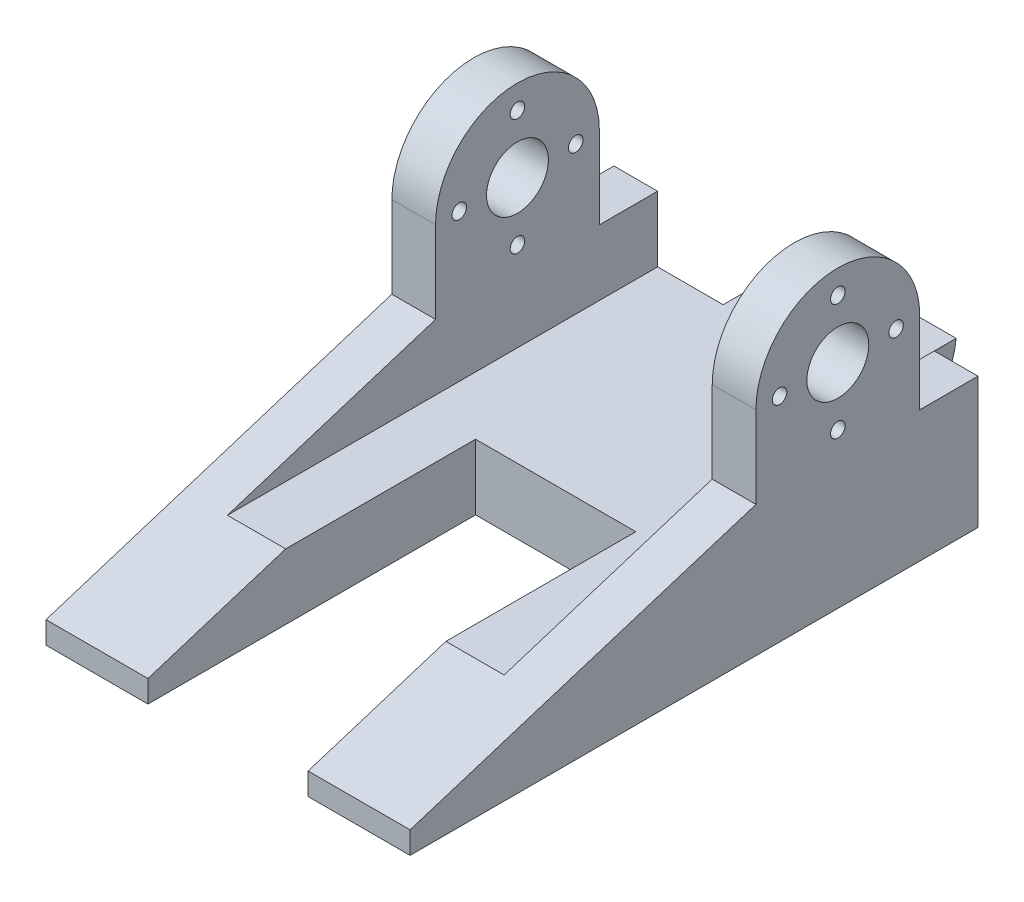
SolidWorks part; units mm, degrees
ref_plane "Front Plane" through (0, 0, 0) normal (0, 0, 1) x (1, 0, 0)
ref_plane "Top Plane" through (0, 0, 0) normal (0, 1, 0) x (1, 0, 0)
ref_plane "Right Plane" through (0, 0, 0) normal (1, 0, 0) x (0, 0, -1)
sketch "Sketch1" plane through (0, 0, 0) normal (0, 0, 1) x (1, 0, 0)
  line L1 (-25, 0) -> (25, 0)
  line L2 (-25, 0) -> (-25, -170)
  line L3 (-25, -170) -> (25, -170)
  line L4 (25, 0) -> (25, -170)
  dimension "D1" = 170
  dimension "D2" = 50
extrude "Boss-Extrude1" add sketch "Sketch1" against normal blind 55
sketch "Sketch2" plane through (0, 0, 0) normal (0, 0, 1) x (1, 0, 0)
  line L0 (25, 0) -> (-25, 0) construction
  line L1 (-17, 0) -> (17, 0)
  line L2 (-17, 0) -> (-17, -27)
  line L3 (-17, -27) -> (17, -27)
  line L4 (17, 0) -> (17, -27)
  line L5 (-25, 0) -> (-25, -170) construction
  dimension "D1" = 8
  dimension "D2" = 34
  dimension "D3" = 27
extrude "Cut-Extrude1" cut sketch "Sketch2" against normal through all
sketch "Sketch3" plane through (25, 0, 0) normal (1, 0, 0) x (0, 0, -1)
  line L0 (0, -170) -> (0, 0) construction
  line L1 (55, -27) -> (0, -27)
  line L2 (55, -27) -> (55, -24)
  line L3 (55, -24) -> (0, -24)
  line L4 (0, -27) -> (0, -24)
  line L5 (55, -170) -> (55, 0) construction
  line L7 (0, 0) -> (10, 0)
  line L8 (0, 0) -> (0, -24)
  line L9 (0, -24) -> (10, -24)
  line L10 (10, 0) -> (10, -24)
  line L11 (55, 0) -> (45, 0)
  line L12 (55, 0) -> (55, -24)
  line L13 (55, -24) -> (45, -24)
  line L14 (45, 0) -> (45, -24)
  circle A0 centre (27.5, -12.75) radius 10.25
  circle A1 centre (27.5, -12.75) radius 4.25
  circle A2 centre (27.5, -12.75) radius 8
  circle A3 centre (27.5, -4.75) radius 1
  circle A4 centre (35.5, -12.75) radius 1
  circle A5 centre (27.5, -20.75) radius 1
  circle A6 centre (19.5, -12.75) radius 1
  point P32 (27.5, -12.75)
  line M7 (0, 0) -> (0, -170)
  line M9 (55, -170) -> (55, 0)
  line M10 (55, 0) -> (0, 0)
  dimension "D2" = 11.25
  dimension "D3" = 27.5
  dimension "D4" = 20.5
  dimension "D7" = 8.5
  dimension "D8" = 16
  dimension "D9" = 4
  dimension "D1" = 3
  dimension "D5" = 10
  dimension "D6" = 10
extrude "Cut-Extrude2" cut sketch "Sketch3" against normal through all contours L14 L3 M10 M9 | L10 L3 M10 M7 | A2 A6 | A2 A6 | A1 | A2 A5 | A2 A5 | A2 A4 | A2 A4 | A2 A3 | A2 A3 region at (25, -12, -50) region at (25, -12, -5) region at (25, -12.75, -27.5) region at (25, -12.75, -35.0645) region at (25, -12.75, -35.913) region at (25, -5.1855, -27.5) region at (25, -4.337, -27.5) region at (25, -21.163, -27.5) region at (25, -20.3145, -27.5) region at (25, -12.75, -19.9355) region at (25, -12.75, -19.087)
sketch "Sketch4" plane through (0, 0, -10) normal (0, 0, 1) x (1, 0, 0)
  line L0 (-25, -24) -> (-17, -24) construction
  line L1 (-17, 0) -> (-19, 0)
  line L2 (-17, 0) -> (-17, -24)
  line L3 (-17, -24) -> (-19, -24)
  line L4 (-19, 0) -> (-19, -24)
  line L5 (0, 0) -> (0, -13.53) construction
  line L6 (19, 0) -> (19, -24)
  line L7 (17, -24) -> (19, -24)
  line L8 (17, 0) -> (17, -24)
  line L9 (17, 0) -> (19, 0)
  dimension "D1" = 2
extrude "Cut-Extrude3" cut sketch "Sketch4" against normal through all
sketch "Sketch5" plane through (25, 0, 0) normal (1, 0, 0) x (0, 0, -1)
  line L1 (10, 0) -> (45, 0)
  line L2 (10, 0) -> (10, -24)
  line L3 (10, -24) -> (45, -24)
  line L4 (45, 0) -> (45, -24)
  line L5 (38.75, -12.75) -> (38.75, -24)
  line L6 (16.25, -12.75) -> (10, -12.75)
  line L7 (16.25, -12.75) -> (16.25, -24)
  line L8 (16.25, -24) -> (10, -24)
  line L9 (10, -12.75) -> (10, -24)
  line L10 (38.75, -12.75) -> (45, -12.75)
  line L11 (38.75, -12.75) -> (38.75, -24)
  line L12 (38.75, -24) -> (45, -24)
  line L13 (45, -12.75) -> (45, -24)
  circle A0 centre (27.5, -12.75) radius 11.25
  line M8 (45, -24) -> (45, 0)
  line M9 (45, 0) -> (10, 0)
  line M10 (10, 0) -> (10, -24)
  dimension "D1" = 22.5
extrude "Cut-Extrude4" cut sketch "Sketch5" against normal through all contours A0 L10 L4 L6 M9 M10 | L7 L6 L2 L3 | L10 L5 L3 M8 region at (25, -0.3725, -27.5) region at (25, -18.375, -13.125) region at (25, -18.375, -41.875)
sketch "Sketch6" plane through (0, 0, 0) normal (0, 0, 1) x (1, 0, 0)
  line L1 (-19, -24) -> (19, -24)
  line L2 (-19, -24) -> (-19, -34)
  line L3 (-19, -34) -> (19, -34)
  line L4 (19, -24) -> (19, -34)
  dimension "D1" = 10
extrude "Cut-Extrude5" cut sketch "Sketch6" against normal through all
sketch "Sketch8" plane through (25, 0, 0) normal (1, 0, 0) x (0, 0, -1)
  line L0 (55, -170) -> (55, -24) construction
  line L1 (0, -170) -> (0, -24) construction
  line L2 (41.75, -132.5) -> (13.25, -132.5)
  line L3 (27.5, -132.5) -> (27.5, -179)
  line L4 (41.75, -179) -> (13.25, -179)
  line L5 (13.25, -132.5) -> (13.25, -179)
  line L7 (41.75, -132.5) -> (41.75, -179)
  line L11 (27.5, -167.75) -> (55, -167.75)
  line L12 (27.5, -167.75) -> (27.5, -170)
  line L13 (27.5, -170) -> (55, -170)
  line L14 (55, -167.75) -> (55, -170)
  line L16 (27.5, -167.75) -> (0, -167.75)
  line L17 (27.5, -167.75) -> (27.5, -170)
  line L18 (27.5, -170) -> (0, -170)
  line L19 (0, -167.75) -> (0, -170)
  circle A0 centre (27.5, -167.75) radius 10.25
  circle A1 centre (27.5, -12.75) radius 10.25
  line M4 (0, -24) -> (0, -170)
  line M5 (0, -170) -> (55, -170)
  line M6 (55, -170) -> (55, -24)
  dimension "D1" = 27.5
  dimension "D2" = 20.5
  dimension "D3" = 155
  dimension "D4" = 14.25
  dimension "D5" = 11.25
  dimension "D6" = 46.5
  dimension "D7" = 13.25
extrude "Cut-Extrude7" cut sketch "Sketch8" against normal through all contours A0 L3 L2 L5 L16 | A0 L11 L7 L2 L3 | L11 L7 M5 M6 | L5 L16 M4 M5 | A0 L16 L5 M5 | A0 L13 L7 L11 | L3 A0 L16 | L11 A0 L3 | L16 A0 L18 L3 | A0 L11 L3 M5 region at (25, -147.5157, -35.1704) region at (25, -147.5157, -19.8296) region at (25, -168.875, -48.375) region at (25, -168.8865, -39.7079) region at (25, -163.3998, -31.8502) region at (25, -163.3998, -23.1498) region at (25, -168.8704, -32.5838) region at (25, -168.8865, -15.2921) region at (25, -168.875, -6.625) region at (25, -168.8704, -22.4162)
sketch "Sketch9" plane through (0, 0, 0) normal (0, 0, 1) x (1, 0, 0)
  line L0 (-25, -167.75) -> (25, -167.75) construction
  line L1 (17, -167.75) -> (-17, -167.75)
  line L2 (17, -167.75) -> (17, -132.5)
  line L3 (17, -132.5) -> (-17, -132.5)
  line L4 (-17, -167.75) -> (-17, -132.5)
  line L5 (-25, -132.5) -> (25, -132.5) construction
  line L7 (-25, -24) -> (-25, -167.75) construction
  line L9 (25, -167.75) -> (25, -24) construction
  dimension "D1" = 8
  dimension "D2" = 8
extrude "Cut-Extrude8" cut sketch "Sketch9" against normal through all
sketch "Sketch11" plane through (25, 0, 0) normal (1, 0, 0) x (0, 0, -1)
  line L0 (27.5, -157.5) -> (27.5, -147.5)
  line L2 (27.5, -147.5) -> (55, -147.5)
  line L3 (27.5, -147.5) -> (27.5, -167.75)
  line L4 (27.5, -167.75) -> (55, -167.75)
  line L5 (55, -147.5) -> (55, -167.75)
  line L6 (27.5, -147.5) -> (0, -147.5)
  line L7 (27.5, -147.5) -> (27.5, -167.75)
  line L8 (27.5, -167.75) -> (0, -167.75)
  line L9 (0, -147.5) -> (0, -167.75)
  circle A0 centre (27.5, -167.75) radius 10.25
  arc A1 (38.75, -12.75) -> (16.25, -12.75) centre (27.5, -12.75) ccw construction
  line M1 (0, -167.75) -> (13.25, -167.75)
  line M2 (13.25, -167.75) -> (13.25, -132.5)
  line M4 (41.75, -132.5) -> (41.75, -167.75)
  line M5 (41.75, -167.75) -> (55, -167.75)
  line M6 (55, -167.75) -> (55, -24)
  line M12 (0, -24) -> (0, -167.75)
  dimension "D1" = 155
  dimension "D2" = 20.5
  dimension "D3" = 10
extrude "Cut-Extrude9" cut sketch "Sketch11" against normal through all contours A0 L0 L6 L8 M2 | A0 L4 L2 L0 M4 | L2 M4 M5 M6 | L6 M2 M12 M1 region at (25, -155.3124, -19.2638) region at (25, -155.3124, -35.7362) region at (25, -157.625, -48.375) region at (25, -157.625, -6.625)
sketch "Sketch12" plane through (25, 0, 0) normal (1, 0, 0) x (0, 0, -1)
  line L1 (13.25, -132.5) -> (41.75, -132.5)
  line L2 (13.25, -132.5) -> (13.25, -147.5)
  line L3 (13.25, -147.5) -> (41.75, -147.5)
  line L4 (41.75, -132.5) -> (41.75, -147.5)
extrude "Boss-Extrude2" add sketch "Sketch12" against normal blind 8
ref_plane "Plane1" through (0, 0, 0) normal (1, 0, 0) x (0, 0, -1)
mirror "Mirror1" about plane through (0, 0, 0) normal (1, 0, 0) of "Boss-Extrude2"
sketch "Sketch14" plane through (0, 0, 0) normal (0, 0, 1) x (1, 0, 0)
  line L0 (17, -148.55) -> (17, -158.75) construction
  line L1 (-17, -132.5) -> (17, -132.5)
  line L2 (-17, -132.5) -> (-17, -147.5)
  line L3 (-17, -147.5) -> (17, -147.5)
  line L4 (17, -132.5) -> (17, -147.5)
  line L5 (-17, -147.5) -> (17, -147.5)
  line L6 (-17, -147.5) -> (-17, -157.75)
  line L7 (-17, -157.75) -> (17, -157.75)
  line L8 (17, -147.5) -> (17, -157.75)
  line M11 (-17, -147.5) -> (-17, -132.5)
  line M12 (-17, -132.5) -> (17, -132.5)
  line M13 (17, -132.5) -> (17, -147.5)
  dimension "D1" = 10.25
extrude "Boss-Extrude3" add sketch "Sketch14" against normal blind 13.25 contours L3 M11 M13 M12 | L8 L3 L6 L7 region at (0, -140, 0) region at (0, -152.625, 0)
ref_plane "Plane2" through (0, 0, -27.5) normal (0, 0, 1) x (1, 0, 0)
mirror "Mirror2" about plane through (0, 0, -27.5) normal (0, 0, 1) of "Boss-Extrude3"
sketch "Sketch16" plane through (25, 0, 0) normal (1, 0, 0) x (0, 0, -1)
  line L0 (41.75, -132.5) -> (13.25, -132.5) construction
  line L1 (13.25, -132.5) -> (13.25, -147.5) construction
  circle A1 centre (16.5, -135.75) radius 2.5
  circle A2 centre (16.5, -135.75) radius 4.5
  circle A3 centre (38.5, -135.75) radius 4.5
  dimension "D1" = 3.25
  dimension "D2" = 3.25
  dimension "D3" = 2
extrude "Cut-Extrude13" cut sketch "Sketch16" against normal blind 8 contours A1 | A2 A1 | A3 region at (25, -135.75, -16.5) region at (25, -135.75, -12.1273) region at (25, -135.75, -38.5)
mirror "Mirror3" about plane through (0, 0, 0) normal (1, 0, 0) of "Cut-Extrude13"
sketch "Sketch17" plane through (25, 0, 0) normal (1, 0, 0) x (0, 0, -1)
  line L0 (55, -147.5) -> (55, -24) construction
  line L1 (27.5, -1.5) -> (55, -1.5)
  line L2 (27.5, -1.5) -> (27.5, -51.5)
  line L3 (27.5, -51.5) -> (55, -51.5)
  line L4 (55, -1.5) -> (55, -51.5)
  line L8 (55, -51.5) -> (0, -51.5)
  line L9 (55, -51.5) -> (55, -157.75)
  line L10 (55, -157.75) -> (0, -157.75)
  line L11 (0, -51.5) -> (0, -157.75)
  arc A0 (38.75, -12.75) -> (16.25, -12.75) centre (27.5, -12.75) ccw construction
  circle M2 centre (16.5, -135.75) radius 4.5
  circle M3 centre (38.5, -135.75) radius 4.5
  line M4 (0, -147.5) -> (55, -147.5)
  line M5 (55, -147.5) -> (55, -24)
  line M11 (0, -24) -> (0, -147.5)
  dimension "D1" = 50
extrude "Cut-Extrude15" cut sketch "Sketch17" against normal through all contours L3 L8 M11 M4 M5 M2 M3 | L11 L10 L9 M4 | M3 | M2 region at (25, -98.6049, -27.5) region at (25, -152.625, -27.5) region at (25, -135.75, -16.5) region at (25, -135.75, -38.5)
sketch "Sketch18" plane through (25, 0, 0) normal (1, 0, 0) x (0, 0, -1)
  line L1 (38.75, -24) -> (-71.25, -24)
  line L2 (38.75, -24) -> (38.75, -51.5)
  line L3 (38.75, -51.5) -> (-71.25, -51.5)
  line L4 (-71.25, -24) -> (-71.25, -51.5)
  line L6 (38.75, -24) -> (68.75, -24)
  line L7 (38.75, -24) -> (38.75, -51.5)
  line L8 (38.75, -51.5) -> (68.75, -51.5)
  line L9 (68.75, -24) -> (68.75, -51.5)
  line M8 (0, -24) -> (0, -51.5)
  line M9 (0, -51.5) -> (55, -51.5)
  line M10 (55, -51.5) -> (55, -24)
  line M11 (55, -24) -> (38.75, -24)
  line M15 (16.25, -24) -> (0, -24)
  dimension "D1" = 110
  dimension "D2" = 30
extrude "Boss-Extrude4" add sketch "Sketch18" against normal blind 50 contours L1 L4 L3 M8 | L9 L6 L8 M10 | L2 L1 M15 M8 M9 | L2 M11 M9 M10 region at (25, -37.75, -19.375) region at (25, -37.75, -46.875) region at (25, -37.75, -61.875) region at (25, -37.75, 35.625)
sketch "Sketch19" plane through (0, 0, 71.25) normal (0, 0, 1) x (1, 0, 0)
  line L1 (-19, -24) -> (19, -24)
  line L2 (-19, -24) -> (-19, -31)
  line L3 (-19, -31) -> (19, -31)
  line L4 (19, -24) -> (19, -31)
  dimension "D1" = 7
extrude "Cut-Extrude16" cut sketch "Sketch19" against normal through all
sketch "Sketch20" plane through (25, 0, 0) normal (1, 0, 0) x (0, 0, -1)
  line L1 (-71.25, -24) -> (68.75, -24)
  line L2 (-71.25, -24) -> (-71.25, -51.5)
  line L3 (-71.25, -51.5) -> (68.75, -51.5)
  line L4 (68.75, -24) -> (68.75, -51.5)
  line L5 (16.25, -24) -> (-13.75, -24)
  line L6 (16.25, -24) -> (16.25, -51.5)
  line L7 (16.25, -51.5) -> (-13.75, -51.5)
  line L8 (-13.75, -24) -> (-13.75, -51.5)
  line L10 (-13.75, -51.5) -> (-71.25, -51.5)
  line L11 (-13.75, -51.5) -> (-13.75, -24)
  line L12 (-13.75, -24) -> (-71.25, -24)
  line L13 (-71.25, -51.5) -> (-71.25, -24)
  line M8 (-71.25, -24) -> (-71.25, -51.5)
  line M9 (-71.25, -51.5) -> (68.75, -51.5)
  dimension "D1" = 30
extrude "Cut-Extrude17" cut sketch "Sketch20" against normal through all contours L8 L1 M8 M9 region at (25, -37.75, 42.5)
sketch "Sketch21" plane through (25, 0, 0) normal (1, 0, 0) x (0, 0, -1)
  line L0 (16.25, -24) -> (-13.75, -51.5)
  line L1 (16.25, -24) -> (-13.75, -24)
  line L2 (16.25, -24) -> (16.25, -51.5)
  line L3 (16.25, -51.5) -> (-13.75, -51.5)
  line L4 (-13.75, -24) -> (-13.75, -51.5)
  line M6 (16.25, -24) -> (-13.75, -24)
  line M7 (-13.75, -24) -> (-13.75, -51.5)
extrude "Cut-Extrude18" cut sketch "Sketch21" against normal through all contours L0 M6 M7 region at (25, -33.1667, 3.75)
sketch "Sketch22" plane through (25, 0, 0) normal (1, 0, 0) x (0, 0, -1)
  line L3 (68.75, -51.5) -> (-13.75, -51.5)
  line L4 (68.75, -51.5) -> (68.75, -54)
  line L5 (68.75, -54) -> (-13.75, -54)
  line L6 (-13.75, -51.5) -> (-13.75, -54)
  dimension "D1" = 2.5
extrude "Boss-Extrude5" add sketch "Sketch22" against normal blind 50
sketch "Sketch24" plane through (25, 0, 0) normal (1, 0, 0) x (0, 0, -1)
  line L1 (68.75, -24) -> (46.75, -24)
  line L2 (68.75, -24) -> (68.75, -41)
  line L3 (68.75, -41) -> (46.75, -41)
  line L4 (46.75, -24) -> (46.75, -41)
  dimension "D1" = 17
  dimension "D2" = 22
extrude "Cut-Extrude19" cut sketch "Sketch24" against normal through all
sketch "Sketch25" plane through (0, -31, 0) normal (0, 1, 0) x (1, 0, 0)
  line L1 (-19, 46.75) -> (19, 46.75)
  line L2 (-19, 46.75) -> (-19, 8.6136)
  line L3 (-19, 8.6136) -> (19, 8.6136)
  line L4 (19, 46.75) -> (19, 8.6136)
extrude "Cut-Extrude20" cut sketch "Sketch25" against normal blind 10
sketch "Sketch27" plane through (0, -41, 0) normal (0, 1, 0) x (1, 0, 0)
  line L0 (-25, 68.75) -> (25, 68.75) construction
  line L1 (19, 8.6136) -> (-19, 8.6136)
  line L2 (19, 8.6136) -> (19, 68.75)
  line L3 (19, 68.75) -> (-19, 68.75)
  line L4 (-19, 8.6136) -> (-19, 68.75)
extrude "Boss-Extrude6" add sketch "Sketch27" along normal blind 8.6
sketch "Sketch29" plane through (0, 0, -8.6136) normal (0, 0, -1) x (-1, 0, 0)
  line L1 (-19, -31) -> (19, -31)
  line L2 (-19, -31) -> (-19, -32.4)
  line L3 (-19, -32.4) -> (19, -32.4)
  line L4 (19, -31) -> (19, -32.4)
extrude "Cut-Extrude21" cut sketch "Sketch29" against normal through all
sketch "Sketch30" plane through (-25, 0, 0) normal (-1, 0, 0) x (0, 0, 1)
  line L0 (-68.75, -32.4) -> (-68.75, -41) construction
  line L1 (-38.75, -24) -> (31.25, -24)
  line L2 (-38.75, -24) -> (-38.75, -53.9144)
  line L3 (-38.75, -53.9144) -> (31.25, -53.9144)
  line L4 (31.25, -24) -> (31.25, -53.9144)
  line L5 (-16.25, -24) -> (31.25, -38.9572)
  line L6 (31.25, -38.9572) -> (31.25, -53.9144)
  line L7 (-16.25, -24) -> (-16.25, -32.4)
  line L8 (-46.75, -32.4) -> (-7.0864, -32.4) construction
  line L9 (-16.25, -32.4) -> (-7.0864, -32.4)
  line L10 (-7.0864, -32.4) -> (-16.25, -24)
  line M5 (13.75, -54) -> (13.75, -51.5)
  line M6 (13.75, -51.5) -> (-16.25, -24)
  dimension "D1" = 100
extrude "Boss-Extrude7" add sketch "Sketch30" against normal blind 50 contours L5 L3 L4 M6 M5 | L7 L9 L10 region at (-25, -40.9436, 13.5151)
sketch "Sketch31" plane through (0, 0, -68.75) normal (0, 0, -1) x (-1, 0, 0)
  line L1 (-19, -24) -> (19, -24)
  line L2 (-19, -24) -> (-19, -41)
  line L3 (-19, -41) -> (19, -41)
  line L4 (19, -24) -> (19, -41)
extrude "Cut-Extrude22" cut sketch "Sketch31" against normal through all
sketch "Sketch32" plane through (25, 0, 0) normal (1, 0, 0) x (0, 0, -1)
  line L0 (-31.25, -38.9572) -> (-31.25, -53.9144) construction
  line L1 (68.75, -54) -> (-31.25, -54)
  line L2 (68.75, -54) -> (68.75, -51)
  line L3 (68.75, -51) -> (-31.25, -51)
  line L4 (-31.25, -54) -> (-31.25, -51)
  dimension "D1" = 3
extrude "Cut-Extrude23" cut sketch "Sketch32" against normal through all
sketch "Sketch33" plane through (0, -41, 0) normal (0, 1, 0) x (1, 0, 0)
  line L0 (19, -31.25) -> (-19, -31.25) construction
  line L1 (11, -31.25) -> (-11, -31.25)
  line L2 (11, -31.25) -> (11, 13.75)
  line L3 (11, 13.75) -> (-11, 13.75)
  line L4 (-11, -31.25) -> (-11, 13.75)
  line L6 (-25, 68.75) -> (-10, 68.75)
  line L7 (-25, 68.75) -> (-25, 46.75)
  line L8 (-25, 46.75) -> (-10, 46.75)
  line L9 (-10, 68.75) -> (-10, 46.75)
  line L10 (25, 68.75) -> (10, 68.75)
  line L11 (25, 68.75) -> (25, 46.75)
  line L12 (25, 46.75) -> (10, 46.75)
  line L13 (10, 68.75) -> (10, 46.75)
  line L15 (19, 16.25) -> (19, -31.25) construction
  line L16 (-19, -31.25) -> (-19, 46.75) construction
  line L18 (-10, 68.75) -> (10, 68.75)
  line L19 (-10, 68.75) -> (-10, 58.75)
  line L20 (-10, 58.75) -> (10, 58.75)
  line L21 (10, 68.75) -> (10, 58.75)
  line M10 (-25, 46.75) -> (-19, 46.75)
  line M12 (-19, -31.25) -> (19, -31.25)
  line M14 (19, 46.75) -> (25, 46.75)
  line M15 (25, 46.75) -> (25, 68.75)
  line M16 (25, 68.75) -> (-25, 68.75)
  line M17 (-25, 68.75) -> (-25, 46.75)
  dimension "D1" = 8
  dimension "D2" = 8
  dimension "D3" = 45
  dimension "D4" = 15
  dimension "D5" = 15
  dimension "D6" = 10
extrude "Cut-Extrude24" cut sketch "Sketch33" against normal through all contours L9 L8 M16 M17 M10 | L13 L12 M16 M14 M15 | L9 L20 L13 M16 | L4 L2 L3 M12 region at (0, -41, 8.75) region at (-17.5, -41, -57.75) region at (0, -41, -63.75) region at (17.5, -41, -57.75)
sketch "Sketch34" plane through (0, -41, 0) normal (0, 1, 0) x (1, 0, 0)
  line L0 (-10, 58.75) -> (10, 58.75) construction
  line L1 (-4, 58.75) -> (4, 58.75)
  line L2 (-4, 58.75) -> (-4, 46.75)
  line L3 (-4, 46.75) -> (4, 46.75)
  line L4 (4, 58.75) -> (4, 46.75)
  line L5 (-10, 58.75) -> (-10, 46.75) construction
  line L6 (10, 58.75) -> (10, 46.75) construction
  dimension "D1" = 6
  dimension "D2" = 6
  dimension "D3" = 12
extrude "Cut-Extrude25" cut sketch "Sketch34" against normal through all
sketch "Sketch36" plane through (0, -41, 0) normal (0, 1, 0) x (1, 0, 0)
  line L1 (19, -31.25) -> (-19, -31.25)
  line L2 (19, -31.25) -> (19, 58.75)
  line L3 (19, 58.75) -> (-19, 58.75)
  line L4 (-19, -31.25) -> (-19, 58.75)
  line L5 (-4, 58.75) -> (4, 58.75)
  line L6 (-4, 58.75) -> (-4, 46.75)
  line L7 (-4, 46.75) -> (4, 46.75)
  line L8 (4, 58.75) -> (4, 46.75)
  line L9 (10, 58.75) -> (19, 58.75)
  line L10 (10, 58.75) -> (10, 46.75)
  line L11 (10, 46.75) -> (19, 46.75)
  line L12 (19, 58.75) -> (19, 46.75)
  line L13 (-10, 58.75) -> (-19, 58.75)
  line L14 (-10, 58.75) -> (-10, 46.75)
  line L15 (-10, 46.75) -> (-19, 46.75)
  line L16 (-19, 58.75) -> (-19, 46.75)
  line L17 (-11, 13.75) -> (11, 13.75)
  line L18 (-11, 13.75) -> (-11, -31.25)
  line L19 (-11, -31.25) -> (11, -31.25)
  line L20 (11, 13.75) -> (11, -31.25)
  line M1 (4, 46.75) -> (-4, 46.75)
  line M2 (-4, 46.75) -> (-4, 58.75)
  line M3 (-4, 58.75) -> (-10, 58.75)
  line M4 (-10, 58.75) -> (-10, 46.75)
  line M5 (-10, 46.75) -> (-19, 46.75)
  line M6 (-19, 46.75) -> (-19, -31.25)
  line M7 (-19, -31.25) -> (-11, -31.25)
  line M8 (-11, -31.25) -> (-11, 13.75)
  line M9 (-11, 13.75) -> (11, 13.75)
  line M10 (11, 13.75) -> (11, -31.25)
  line M11 (11, -31.25) -> (19, -31.25)
  line M12 (19, -31.25) -> (19, 46.75)
  line M13 (19, 46.75) -> (10, 46.75)
  line M14 (10, 46.75) -> (10, 58.75)
  line M15 (10, 58.75) -> (4, 58.75)
  line M16 (4, 58.75) -> (4, 46.75)
extrude "Boss-Extrude8" add sketch "Sketch36" along normal blind 8 contours M16 M1 M2 M3 M4 M5 M6 M7 M8 M9 M10 M11 M12 M13 M14 M15 region at (0, -41, -18.522)
sketch "Sketch37" plane through (25, 0, 0) normal (1, 0, 0) x (0, 0, -1)
  line L0 (-31.25, -38.9572) -> (-31.25, -51) construction
  line L1 (58.75, -51) -> (-31.25, -51)
  line L2 (58.75, -51) -> (58.75, -42)
  line L3 (58.75, -42) -> (-31.25, -42)
  line L4 (-31.25, -51) -> (-31.25, -42)
  line L5 (-31.25, -38.9572) -> (-12.3315, -33)
  line L6 (-12.3315, -33) -> (-31.25, -33)
  line L7 (-12.3315, -33) -> (-12.3315, -38.9572)
  line L8 (-12.3315, -38.9572) -> (-31.25, -38.9572)
  line L9 (-31.25, -33) -> (-31.25, -38.9572)
  line L11 (58.75, -42) -> (46.75, -42)
  line L12 (58.75, -42) -> (58.75, -51)
  line L13 (58.75, -51) -> (46.75, -51)
  line L14 (46.75, -42) -> (46.75, -51)
  line M7 (-31.25, -51) -> (46.75, -51)
  line M8 (46.75, -51) -> (46.75, -24)
  line M13 (16.25, -24) -> (-31.25, -38.9572)
  line M14 (-31.25, -38.9572) -> (-31.25, -51)
  dimension "D1" = 9
extrude "Cut-Extrude27" cut sketch "Sketch37" against normal through all contours L3 M8 M14 M7 | L6 L9 M13 | L2 L3 L1 M8 region at (25, -34.9857, 24.9438) region at (25, -46.5, -52.75) region at (25, -46.5, -7.75)
fillet "Fillet1" radius 10 2 edges at (-7, -42, -58.75) (7, -42, -58.75)
